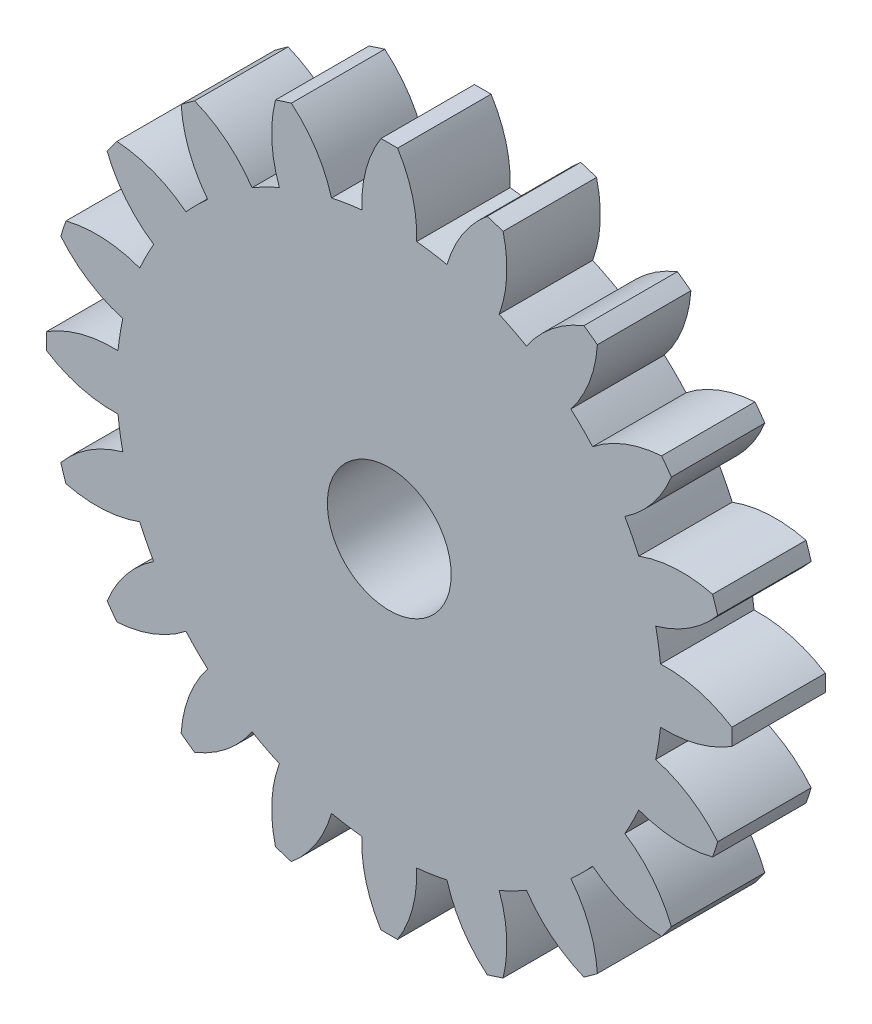
SolidWorks part; units mm, degrees
ref_plane "Front Plane" through (0, 0, 0) normal (0, 0, 1) x (1, 0, 0)
ref_plane "Top Plane" through (0, 0, 0) normal (0, 1, 0) x (1, 0, 0)
ref_plane "Right Plane" through (0, 0, 0) normal (1, 0, 0) x (0, 0, -1)
sketch "Sketch1" plane through (0, 0, 0) normal (0, 0, 1) x (1, 0, 0)
  point P0 (0, 22)
  arc B0 (12.4951, 18.1072) -> (8.8104, 15.1192) centre (15.4651, 10.679) ccw
  arc B1 (8.8104, 15.1192) -> (7.0531, 16.0147) centre (0, 0) ccw
  arc B2 (7.0531, 16.0147) -> (7.3046, 20.7519) centre (-0.4507, 18.7884) ccw
  arc B3 (7.3046, 20.7519) -> (6.2881, 21.0822) centre (0, 0) ccw
  arc B4 (6.2881, 21.0822) -> (3.7071, 17.1018) centre (11.4082, 14.9353) ccw
  arc B5 (3.7071, 17.1018) -> (1.7591, 17.4104) centre (0, 0) ccw
  arc B6 (1.7591, 17.4104) -> (0.5344, 21.9935) centre (-6.2346, 17.7296) ccw
  arc B7 (0.5344, 21.9935) -> (-0.5344, 21.9935) centre (0, 0) ccw
  arc B8 (-0.5344, 21.9935) -> (-1.7591, 17.4104) centre (6.2346, 17.7296) ccw
  arc B9 (-1.7591, 17.4104) -> (-3.7071, 17.1018) centre (0, 0) ccw
  arc B10 (-3.7071, 17.1018) -> (-6.2881, 21.0822) centre (-11.4082, 14.9353) ccw
  arc B11 (-6.2881, 21.0822) -> (-7.3046, 20.7519) centre (0, 0) ccw
  arc B12 (-7.3046, 20.7519) -> (-7.0531, 16.0147) centre (0.4507, 18.7884) ccw
  arc B13 (-7.0531, 16.0147) -> (-8.8104, 15.1192) centre (0, 0) ccw
  arc B14 (-8.8104, 15.1192) -> (-12.4951, 18.1072) centre (-15.4651, 10.679) ccw
  arc B15 (-12.4951, 18.1072) -> (-13.3598, 17.479) centre (0, 0) ccw
  arc B16 (-13.3598, 17.479) -> (-11.6567, 13.0513) centre (-5.3773, 18.0081) ccw
  arc B17 (-11.6567, 13.0513) -> (-13.0513, 11.6567) centre (0, 0) ccw
  arc B18 (-13.0513, 11.6567) -> (-17.479, 13.3598) centre (-18.0081, 5.3773) ccw
  arc B19 (-17.479, 13.3598) -> (-18.1072, 12.4951) centre (0, 0) ccw
  arc B20 (-18.1072, 12.4951) -> (-15.1192, 8.8104) centre (-10.679, 15.4651) ccw
  arc B21 (-15.1192, 8.8104) -> (-16.0147, 7.0531) centre (0, 0) ccw
  arc B22 (-16.0147, 7.0531) -> (-20.7519, 7.3046) centre (-18.7884, -0.4507) ccw
  arc B23 (-20.7519, 7.3046) -> (-21.0822, 6.2881) centre (0, 0) ccw
  arc B24 (-21.0822, 6.2881) -> (-17.1018, 3.7071) centre (-14.9353, 11.4082) ccw
  arc B25 (-17.1018, 3.7071) -> (-17.4104, 1.7591) centre (0, 0) ccw
  arc B26 (-17.4104, 1.7591) -> (-21.9935, 0.5344) centre (-17.7296, -6.2346) ccw
  arc B27 (-21.9935, 0.5344) -> (-21.9935, -0.5344) centre (0, 0) ccw
  arc B28 (-21.9935, -0.5344) -> (-17.4104, -1.7591) centre (-17.7296, 6.2346) ccw
  arc B29 (-17.4104, -1.7591) -> (-17.1018, -3.7071) centre (0, 0) ccw
  arc B30 (-17.1018, -3.7071) -> (-21.0822, -6.2881) centre (-14.9353, -11.4082) ccw
  arc B31 (-21.0822, -6.2881) -> (-20.7519, -7.3046) centre (0, 0) ccw
  arc B32 (-20.7519, -7.3046) -> (-16.0147, -7.0531) centre (-18.7884, 0.4507) ccw
  arc B33 (-16.0147, -7.0531) -> (-15.1192, -8.8104) centre (0, 0) ccw
  arc B34 (-15.1192, -8.8104) -> (-18.1072, -12.4951) centre (-10.679, -15.4651) ccw
  arc B35 (-18.1072, -12.4951) -> (-17.479, -13.3598) centre (0, 0) ccw
  arc B36 (-17.479, -13.3598) -> (-13.0513, -11.6567) centre (-18.0081, -5.3773) ccw
  arc B37 (-13.0513, -11.6567) -> (-11.6567, -13.0513) centre (0, 0) ccw
  arc B38 (-11.6567, -13.0513) -> (-13.3598, -17.479) centre (-5.3773, -18.0081) ccw
  arc B39 (-13.3598, -17.479) -> (-12.4951, -18.1072) centre (0, 0) ccw
  arc B40 (-12.4951, -18.1072) -> (-8.8104, -15.1192) centre (-15.4651, -10.679) ccw
  arc B41 (-8.8104, -15.1192) -> (-7.0531, -16.0147) centre (0, 0) ccw
  arc B42 (-7.0531, -16.0147) -> (-7.3046, -20.7519) centre (0.4507, -18.7884) ccw
  arc B43 (-7.3046, -20.7519) -> (-6.2881, -21.0822) centre (0, 0) ccw
  arc B44 (-6.2881, -21.0822) -> (-3.7071, -17.1018) centre (-11.4082, -14.9353) ccw
  arc B45 (-3.7071, -17.1018) -> (-1.7591, -17.4104) centre (0, 0) ccw
  arc B46 (-1.7591, -17.4104) -> (-0.5344, -21.9935) centre (6.2346, -17.7296) ccw
  arc B47 (-0.5344, -21.9935) -> (0.5344, -21.9935) centre (0, 0) ccw
  arc B48 (0.5344, -21.9935) -> (1.7591, -17.4104) centre (-6.2346, -17.7296) ccw
  arc B49 (1.7591, -17.4104) -> (3.7071, -17.1018) centre (0, 0) ccw
  arc B50 (3.7071, -17.1018) -> (6.2881, -21.0822) centre (11.4082, -14.9353) ccw
  arc B51 (6.2881, -21.0822) -> (7.3046, -20.7519) centre (0, 0) ccw
  arc B52 (7.3046, -20.7519) -> (7.0531, -16.0147) centre (-0.4507, -18.7884) ccw
  arc B53 (7.0531, -16.0147) -> (8.8104, -15.1192) centre (0, 0) ccw
  arc B54 (8.8104, -15.1192) -> (12.4951, -18.1072) centre (15.4651, -10.679) ccw
  arc B55 (12.4951, -18.1072) -> (13.3598, -17.479) centre (0, 0) ccw
  arc B56 (13.3598, -17.479) -> (11.6567, -13.0513) centre (5.3773, -18.0081) ccw
  arc B57 (11.6567, -13.0513) -> (13.0513, -11.6567) centre (0, 0) ccw
  arc B58 (13.0513, -11.6567) -> (17.479, -13.3598) centre (18.0081, -5.3773) ccw
  arc B59 (17.479, -13.3598) -> (18.1072, -12.4951) centre (0, 0) ccw
  arc B60 (18.1072, -12.4951) -> (15.1192, -8.8104) centre (10.679, -15.4651) ccw
  arc B61 (15.1192, -8.8104) -> (16.0147, -7.0531) centre (0, 0) ccw
  arc B62 (16.0147, -7.0531) -> (20.7519, -7.3046) centre (18.7884, 0.4507) ccw
  arc B63 (20.7519, -7.3046) -> (21.0822, -6.2881) centre (0, 0) ccw
  arc B64 (21.0822, -6.2881) -> (17.1018, -3.7071) centre (14.9353, -11.4082) ccw
  arc B65 (17.1018, -3.7071) -> (17.4104, -1.7591) centre (0, 0) ccw
  arc B66 (17.4104, -1.7591) -> (21.9935, -0.5344) centre (17.7296, 6.2346) ccw
  arc B67 (21.9935, -0.5344) -> (21.9935, 0.5344) centre (0, 0) ccw
  arc B68 (21.9935, 0.5344) -> (17.4104, 1.7591) centre (17.7296, -6.2346) ccw
  arc B69 (17.4104, 1.7591) -> (17.1018, 3.7071) centre (0, 0) ccw
  arc B70 (17.1018, 3.7071) -> (21.0822, 6.2881) centre (14.9353, 11.4082) ccw
  arc B71 (21.0822, 6.2881) -> (20.7519, 7.3046) centre (0, 0) ccw
  arc B72 (20.7519, 7.3046) -> (16.0147, 7.0531) centre (18.7884, -0.4507) ccw
  arc B73 (16.0147, 7.0531) -> (15.1192, 8.8104) centre (0, 0) ccw
  arc B74 (15.1192, 8.8104) -> (18.1072, 12.4951) centre (10.679, 15.4651) ccw
  arc B75 (18.1072, 12.4951) -> (17.479, 13.3598) centre (0, 0) ccw
  arc B76 (17.479, 13.3598) -> (13.0513, 11.6567) centre (18.0081, 5.3773) ccw
  arc B77 (13.0513, 11.6567) -> (11.6567, 13.0513) centre (0, 0) ccw
  arc B78 (11.6567, 13.0513) -> (13.3598, 17.479) centre (5.3773, 18.0081) ccw
  arc B79 (13.3598, 17.479) -> (12.4951, 18.1072) centre (0, 0) ccw
  circle B80 centre (0, 0) radius 2
sketch_block_instance "Block1-1"
sketch_block "Block1"
extrude "Boss-Extrude1" add sketch "Sketch1" along normal blind 6
sketch "Sketch2" plane through (0, 0, 6) normal (0, 0, 1) x (1, 0, 0)
  circle A0 centre (0, 0) radius 5.1392
extrude "Boss-Extrude2" add sketch "Sketch2" against normal up to surface (6 mm away)
sketch "Sketch3" plane through (0, 0, 6) normal (0, 0, 1) x (1, 0, 0)
  circle A0 centre (0, 0) radius 3.975
  dimension "D1" = 7.95
extrude "Cut-Extrude1" cut sketch "Sketch3" against normal up to surface (6 mm away)
